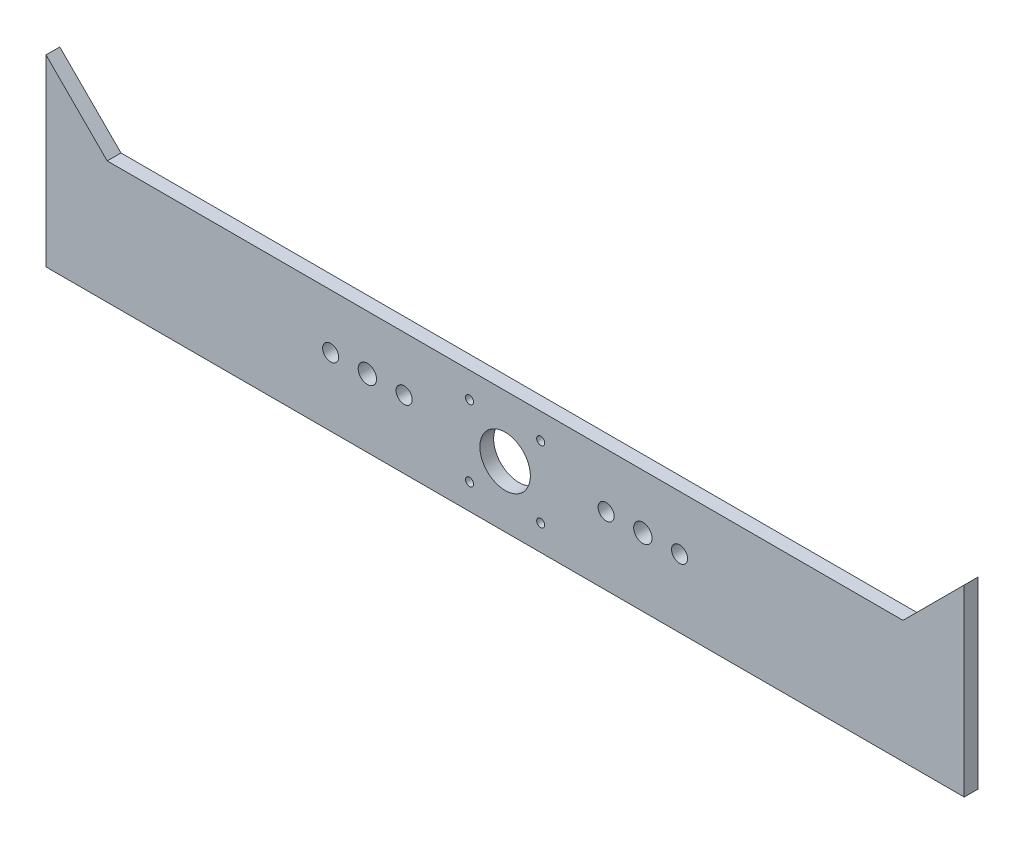
SolidWorks part; units mm, degrees
material "Wrought Stainless Steel"
ref_plane "Front Plane" through (0, 0, 0) normal (0, 0, 1) x (1, 0, 0)
ref_plane "Top Plane" through (0, 0, 0) normal (0, 1, 0) x (1, 0, 0)
ref_plane "Right Plane" through (0, 0, 0) normal (1, 0, 0) x (0, 0, -1)
sketch "Sketch1" plane through (0, 0, 0) normal (0, 0, 1) x (1, 0, 0)
  line L0 (0, -1000) -> (0, 49000) construction
  line L1 (-1000, 0) -> (49000, 0) construction
  line L2 (-1173.1632, 53.3333) -> (48826.8368, 53.3333) construction
  line L3 (-200, 0) -> (200, 0)
  line L4 (-200, 0) -> (-200, 80)
  line L6 (200, 0) -> (200, 80)
  line L7 (200, 80) -> (173.3333, 53.3333)
  line L8 (-200, 80) -> (-173.3333, 53.3333)
  line L9 (-173.3333, 53.3333) -> (173.3333, 53.3333)
  dimension "D1" = 26.6667
  dimension "D2" = 400
  dimension "D3" = 80
  dimension "D5" = 45
extrude "Boss-Extrude1" add sketch "Sketch1" along normal blind 6
sketch "Sketch2" plane through (0, 0, 6) normal (0, 0, 1) x (1, 0, 0)
  line L0 (0, -1000) -> (0, 49000) construction
  line L1 (-1200, 26.665) -> (48800, 26.665) construction
  line L4 (-200, 0) -> (200, 0) construction
  line L5 (44, 29.665) -> (76, 29.665) construction
  circle A0 centre (0, 26.665) radius 11
  circle A1 centre (15.5, 42.165) radius 1.75
  circle A2 centre (-15.5, 42.165) radius 1.75
  circle A3 centre (-15.5, 11.165) radius 1.75
  circle A4 centre (15.5, 11.165) radius 1.75
  circle A5 centre (60, 29.665) radius 4
  circle A6 centre (76, 29.665) radius 3.5
  circle A7 centre (44, 29.665) radius 3.5
  circle A8 centre (-44, 29.665) radius 3.5
  circle A9 centre (-76, 29.665) radius 3.5
  circle A10 centre (-60, 29.665) radius 4
  point P22 (60, 29.665)
  dimension "D1" = 22
  dimension "D5" = 3.5
  dimension "D8" = 8
  dimension "D10" = 7
  dimension "D11" = 7
  dimension "D2" = 26.665
  dimension "D3" = 15.5
  dimension "D4" = 15.5
  dimension "D6" = 3
  dimension "D7" = 60
  dimension "D9" = 32
extrude "Cut-Extrude1" cut sketch "Sketch2" against normal through all
